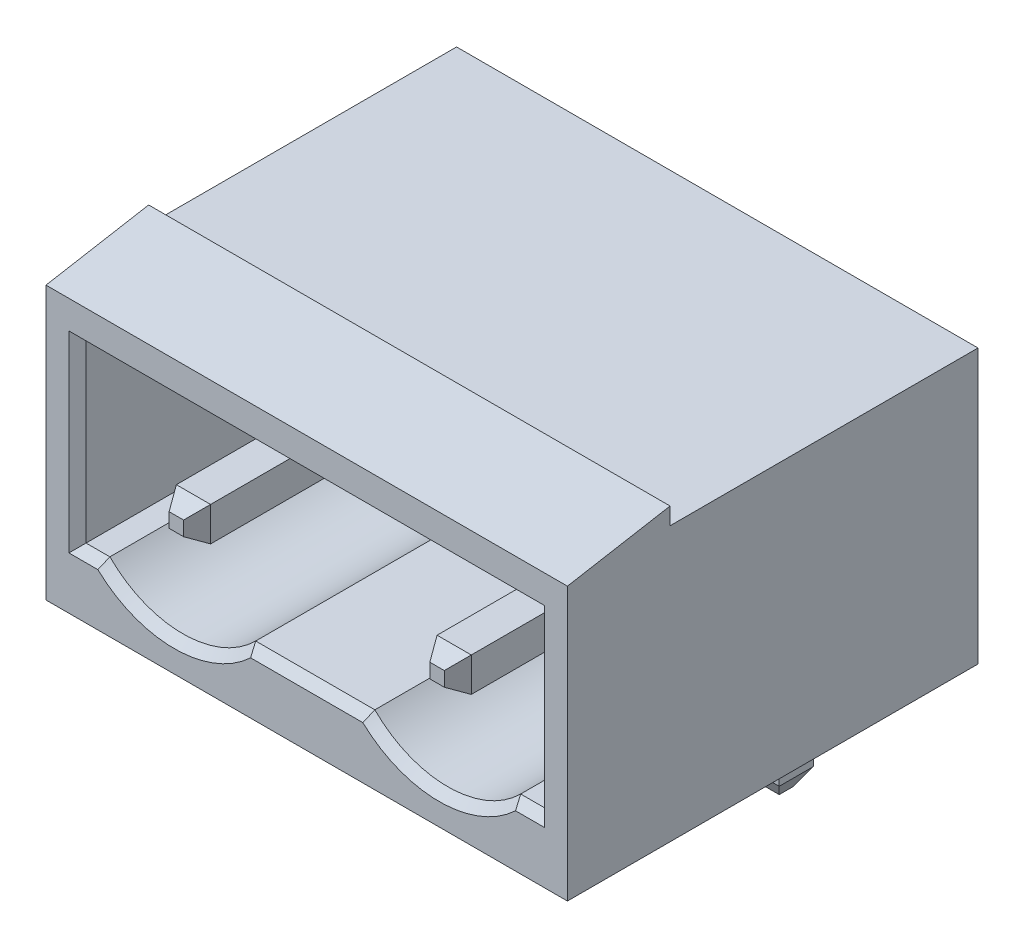
SolidWorks part; units mm, degrees
ref_plane "Plan de face" through (0, 0, 0) normal (0, 0, 1) x (1, 0, 0)
ref_plane "Plan de dessus" through (0, 0, 0) normal (0, 1, 0) x (1, 0, 0)
ref_plane "Plan de droite" through (0, 0, 0) normal (1, 0, 0) x (0, 0, -1)
sketch "Esquisse1" plane through (0, 0, 0) normal (0, 0, 1) x (1, 0, 0)
  line L1 (0, 0) -> (15.24, 0)
  line L2 (0, 0) -> (0, 8.5)
  line L3 (0, 8.5) -> (15.24, 8.5)
  line L4 (15.24, 0) -> (15.24, 8.5)
  dimension "D1" = 15.24
  dimension "D2" = 8.5
extrude "Boss.-Extru.1" add sketch "Esquisse1" along normal blind 12
sketch "Esquisse3" plane through (0, 0, 12) normal (0, 0, 1) x (1, 0, 0)
  line L0 (0, 8.5) -> (0, 0) construction
  line L1 (0.92, 6.8964) -> (14.32, 6.8964)
  line L2 (0.92, 6.8964) -> (0.92, 1.777)
  line L3 (0.92, 1.777) -> (1.6169, 1.777)
  line L5 (5.8788, 1.777) -> (9.3612, 1.777)
  line L6 (3.31, 4.3247) -> (4.31, 4.3247)
  line L7 (3.31, 4.3247) -> (3.31, 3.3247)
  line L8 (3.31, 3.3247) -> (4.31, 3.3247)
  line L9 (4.31, 4.3247) -> (4.31, 3.3247)
  line L10 (10.93, 4.3247) -> (10.93, 3.3247)
  line L11 (11.93, 3.3247) -> (10.93, 3.3247)
  line L12 (11.93, 4.3247) -> (11.93, 3.3247)
  line L13 (11.93, 4.3247) -> (10.93, 4.3247)
  line L14 (14.32, 1.777) -> (13.6231, 1.777)
  line L15 (14.32, 6.8964) -> (14.32, 1.777)
  arc A0 (1.6169, 1.777) -> (5.8788, 1.777) centre (3.7479, 3.908) ccw
  arc A1 (13.6231, 1.777) -> (9.3612, 1.777) centre (11.4921, 3.908) cw
  dimension "D3" = 1
  dimension "D4" = 1
  dimension "D5" = 3.31
extrude "Enlèv. mat.-Extru.1" cut sketch "Esquisse3" against normal blind 7.5
sketch "Esquisse4" plane through (0, 8.5, 0) normal (0, 1, 0) x (-1, 0, 0)
  line L0 (-15.24, 12) -> (-15.24, 0) construction
  line L1 (0, 0) -> (-15.24, 0)
  line L2 (0, 0) -> (0, 9)
  line L3 (0, 9) -> (-15.24, 9)
  line L4 (-15.24, 0) -> (-15.24, 9)
  dimension "D1" = 9
extrude "Enlèv. mat.-Extru.2" cut sketch "Esquisse4" against normal blind 0.5
sketch "Esquisse5" plane through (0, 0, 0) normal (0, -1, 0) x (1, 0, 0)
  line L0 (0, 12) -> (0, 0) construction
  line L1 (3.31, 2.5) -> (4.31, 2.5)
  line L2 (3.31, 2.5) -> (3.31, 1.5)
  line L3 (3.31, 1.5) -> (4.31, 1.5)
  line L4 (4.31, 2.5) -> (4.31, 1.5)
  line L5 (10.93, 2.5) -> (11.93, 2.5)
  line L6 (10.93, 2.5) -> (10.93, 1.5)
  line L7 (10.93, 1.5) -> (11.93, 1.5)
  line L8 (11.93, 2.5) -> (11.93, 1.5)
  line L9 (15.24, 12) -> (15.24, 0) construction
  line L10 (0, 0) -> (15.24, 0) construction
  dimension "D1" = 1
  dimension "D2" = 1
  dimension "D3" = 1
  dimension "D4" = 1
  dimension "D5" = 3.31
  dimension "D6" = 3.31
  dimension "D7" = 1.5
  dimension "D8" = 1.5
extrude "Boss.-Extru.2" add sketch "Esquisse5" along normal blind 4
chamfer "Chanfrein1" distance 0.5 angle 30 8 edges at (11.43, -4, 2.5) (11.93, -4, 2) (11.43, -4, 1.5) (10.93, -4, 2) (3.81, -4, 2.5) (4.31, -4, 2) (3.81, -4, 1.5) (3.31, -4, 2) first distance on face at (11.43, -2, 2.5) first distance on face at (11.93, -2, 2) first distance on face at (11.43, -2, 1.5) first distance on face at (10.93, -2, 2) first distance on face at (3.81, -2, 2.5) first distance on face at (4.31, -2, 2) first distance on face at (3.81, -2, 1.5) first distance on face at (3.31, -2, 2)
chamfer "Chanfrein2" distance 0.5 angle 30 8 edges at (11.93, 3.8247, 12) (11.43, 3.3247, 12) (10.93, 3.8247, 12) (11.43, 4.3247, 12) (3.81, 4.3247, 12) (4.31, 3.8247, 12) (3.81, 3.3247, 12) (3.31, 3.8247, 12) first distance on face at (11.93, 3.8247, 8.25) first distance on face at (11.43, 3.3247, 8.25) first distance on face at (10.93, 3.8247, 8.25) first distance on face at (11.43, 4.3247, 8.25) first distance on face at (3.81, 4.3247, 8.25) first distance on face at (4.31, 3.8247, 8.25) first distance on face at (3.81, 3.3247, 8.25) first distance on face at (3.31, 3.8247, 8.25)
chamfer "Chanfrein3" distance 3 angle 10 1 edges at (7.62, 8.5, 12) first distance on face at (7.62, 8.5, 10.5)
chamfer "Chanfrein4" distance 0.25 angle 45 8 edges at (14.32, 4.3367, 12) (7.62, 6.8964, 12) (13.9715, 1.777, 12) (11.4921, 0.8944, 12) (7.62, 1.777, 12) (3.7479, 0.8944, 12) (1.2685, 1.777, 12) (0.92, 4.3367, 12)
